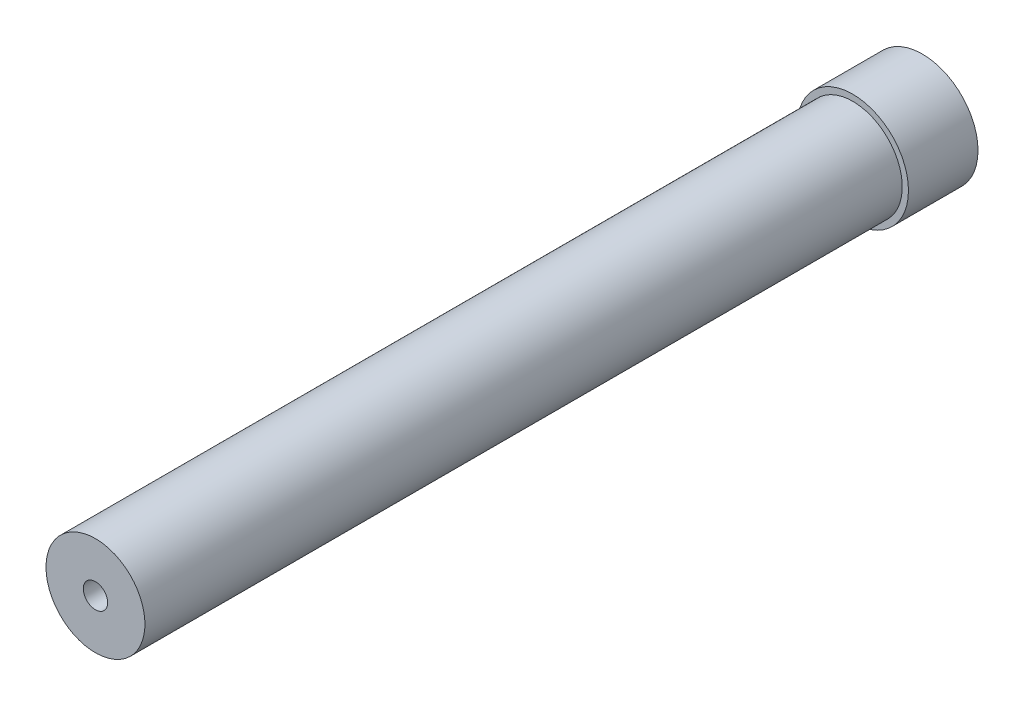
SolidWorks part; units mm, degrees
material "PET"
ref_plane "Front Plane" through (0, 0, 0) normal (0, 0, 1) x (1, 0, 0)
ref_plane "Top Plane" through (0, 0, 0) normal (0, 1, 0) x (1, 0, 0)
ref_plane "Right Plane" through (0, 0, 0) normal (1, 0, 0) x (0, 0, -1)
sketch "Sketch2" plane through (0, 0, 0) normal (0, 0, 1) x (1, 0, 0)
  circle A0 centre (0, 0) radius 9.144
  dimension "D1" = 18.288
extrude "Thicker Section" add sketch "Sketch2" along normal blind 11.43
sketch "Sketch3" plane through (0, 0, 11.43) normal (0, 0, 1) x (1, 0, 0)
  circle A0 centre (0, 0) radius 8.128
  dimension "D1" = 16.256
extrude "Smaller  Section" add sketch "Sketch3" along normal blind 124.46
fillet "Fillet1" [suppressed] radius 2.54
sketch "Sketch4" plane through (0, 0, 135.89) normal (0, 0, 1) x (1, 0, 0)
  circle A0 centre (0, 0) radius 2
  dimension "D1" = 4
extrude "Cut-Extrude1" cut sketch "Sketch4" against normal blind 19.05
